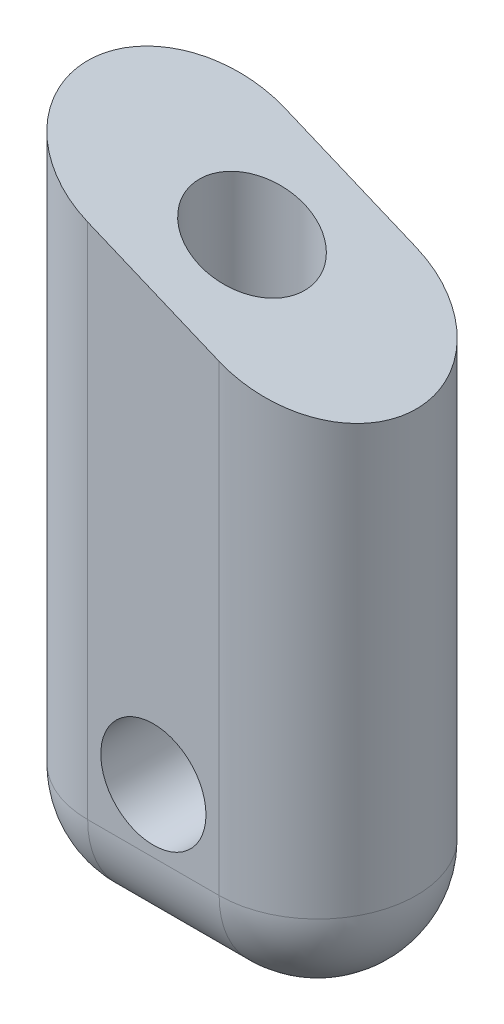
SolidWorks part; units mm, degrees
ref_plane "Front Plane" through (0, 0, 0) normal (0, 0, 1) x (1, 0, 0)
ref_plane "Top Plane" through (0, 0, 0) normal (0, 1, 0) x (1, 0, 0)
ref_plane "Right Plane" through (0, 0, 0) normal (1, 0, 0) x (0, 0, -1)
sketch "Sketch1" plane through (0, 0, 0) normal (0, 1, 0) x (1, 0, 0)
  line L0 (0, 0) -> (4, 0) construction
  line L1 (0, 3) -> (4, 3)
  line L2 (0, -3) -> (4, -3)
  arc A0 (0, 3) -> (0, -3) centre (0, 0) ccw
  arc A1 (4, -3) -> (4, 3) centre (4, 0) ccw
  point P3 (2, 0)
  dimension "D1" = 6
  dimension "D2" = 4
extrude "Boss-Extrude1" add sketch "Sketch1" along normal blind 20
fillet "Fillet3" radius 3 4 edges at (2, 0, -3) (2, 0, 3) (-3, 0, 0) (7, 0, 0)
sketch "Sketch2" plane through (0, 0, 3) normal (0, 0, 1) x (1, 0, 0)
  circle A0 centre (2, 4.926) radius 1.6
  dimension "D1" = 3.2
extrude "Cut-Extrude1" cut sketch "Sketch2" against normal blind 20 contours A0
sketch "Sketch4" plane through (0, 20, 0) normal (0, 1, 0) x (1, 0, 0)
  line L0 (0, -3) -> (4, 3) construction
  line L2 (0, -3) -> (4, -3)
  line L3 (4, 3) -> (0, 3)
  line L4 (0, -3) -> (4, -3)
  line L5 (4, 3) -> (0, 3)
  circle A0 centre (2, 0) radius 1.6
  arc A2 (0, 3) -> (0, -3) centre (0, 0) ccw
  arc A3 (4, -3) -> (4, 3) centre (4, 0) ccw
  arc A4 (0, 3) -> (0, -3) centre (0, 0) ccw
  arc A5 (4, -3) -> (4, 3) centre (4, 0) ccw
  dimension "D2" = 3.2
  dimension "D1" = 0
extrude "Cut-Extrude2" cut sketch "Sketch4" against normal blind 5 contours A0
sketch "Sketch6" plane through (0, 0, 3) normal (0, 0, 1) x (1, 0, 0)
  line L0 (-3, 20) -> (7, 20)
  line L1 (7, 20) -> (7, 15.8175)
  line L2 (7, 3) -> (7, 20) construction
  line L3 (7, 15.8175) -> (-3, 20)
  point P4 (7, 15.8175)
extrude "Cut-Extrude5" cut sketch "Sketch6" against normal blind 100
